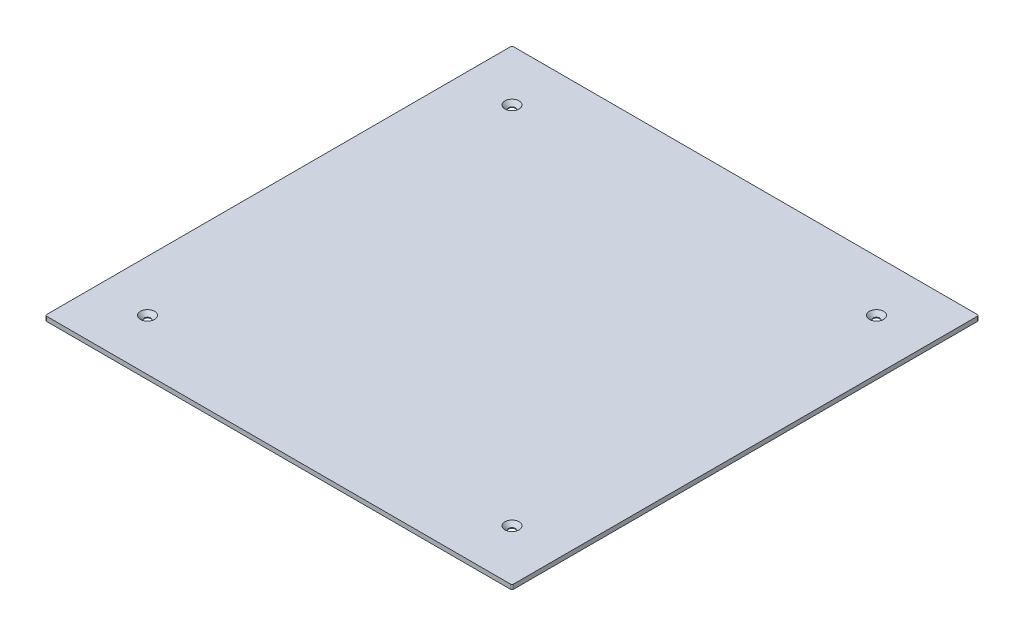
SolidWorks part; units mm, degrees
material "Stop 2014"
ref_plane "Płaszczyzna przednia" through (0, 0, 0) normal (0, 0, 1) x (1, 0, 0)
ref_plane "Płaszczyzna górna" through (0, 0, 0) normal (0, 1, 0) x (1, 0, 0)
ref_plane "Płaszczyzna prawa" through (0, 0, 0) normal (1, 0, 0) x (0, 0, -1)
sketch "Szkic1" plane through (0, 0, 0) normal (0, 1, 0) x (1, 0, 0)
  line L1 (0, 0) -> (310, 0)
  line L2 (0, 0) -> (0, 310)
  line L3 (0, 310) -> (310, 310)
  line L4 (310, 0) -> (310, 310)
  dimension "D1" = 310
  dimension "D2" = 310
extrude "Dodanie-wyciągnięcie1" add sketch "Szkic1" along normal blind 3
fillet "Zaokrąglenie1" radius 1 4 edges at (0, 1.5, -310) (310, 1.5, -310) (310, 1.5, 0) (0, 1.5, 0)
hole_wizard "Pogłębienie stożkowe pod M4 wkręt do części metalowych z łbem soczewkowym1" positions "Szkic2" profile "Szkic3" countersink size "M4" standard "Ansi Metric" end condition through all
sketch "Szkic2" plane through (0, 3, 0) normal (0, 1, 0) x (1, 0, 0)
  line L0 (1, 0) -> (309, 0) construction
  line L1 (0, 309) -> (0, 1) construction
  line L2 (309, 310) -> (1, 310) construction
  line L3 (310, 1) -> (310, 309) construction
  point P0 (34, 276)
  point P2 (34, 34)
  point P4 (276, 34)
  point P6 (276, 276)
  dimension "D1" = 34
  dimension "D2" = 34
  dimension "D3" = 34
  dimension "D4" = 34
  dimension "D5" = 34
  dimension "D6" = 34
  dimension "D7" = 34
  dimension "D8" = 34
sketch "Szkic3" plane through (34, 3, -276) normal (1, 0, 0) x (0, 0, 1)
  line L0 (0, 0) -> (0, 3)
  line L1 (0, 3) -> (2.15, 3)
  line L2 (2.15, 3) -> (2.15, 2.55)
  line L3 (2.15, 2.55) -> (4.7, 0)
  line L5 (4.7, 0) -> (0, 0)
  line L6 (-2.15, 2.55) -> (-4.7, 0) construction
  line L11 (0, -6.35) -> (0, 107.95) construction
  dimension "Œrednica otworu na wylot" = 4.3
  dimension "G³êbokoœæ otworu na wylot" = 3
  dimension "Œrednica zewnêtrznego pog³êbienia sto¿kowego" = 9.4
  dimension "K¹t zewnêtrznego pog³êbienia sto¿kowego" = 90
